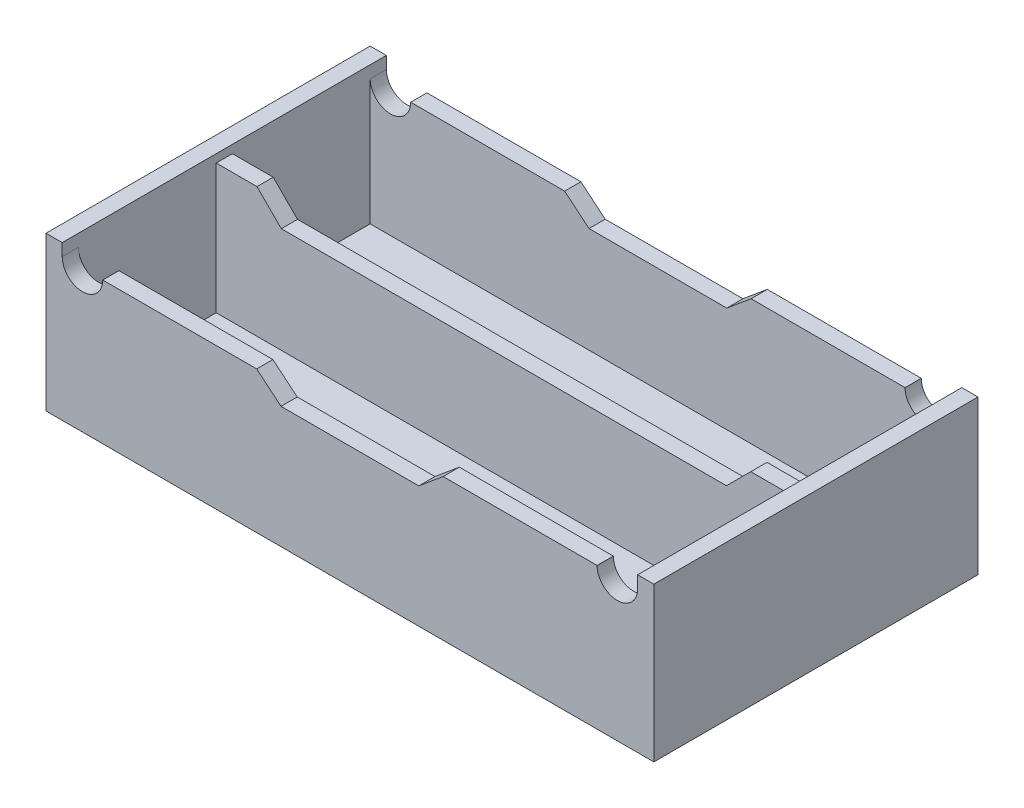
SolidWorks part; units mm, degrees
ref_plane "Front Plane" through (0, 0, 0) normal (0, 0, 1) x (1, 0, 0)
ref_plane "Top Plane" through (0, 0, 0) normal (0, 1, 0) x (1, 0, 0)
ref_plane "Right Plane" through (0, 0, 0) normal (1, 0, 0) x (0, 0, -1)
sketch "Sketch1" plane through (0, 0, 0) normal (0, 1, 0) x (1, 0, 0)
  line L1 (0, 0) -> (75, 0)
  line L2 (0, 0) -> (0, 40)
  line L3 (0, 40) -> (75, 40)
  line L4 (75, 0) -> (75, 40)
  dimension "D1" = 75
  dimension "D2" = 40
extrude "Boss-Extrude1" add sketch "Sketch1" along normal blind 2
sketch "Sketch2" plane through (0, 2, 0) normal (0, 1, 0) x (1, 0, 0)
  line L1 (2, 38) -> (73, 38)
  line L2 (2, 38) -> (2, 21)
  line L3 (2, 21) -> (73, 21)
  line L4 (73, 38) -> (73, 21)
  line L5 (2, 19) -> (73, 19)
  line L6 (2, 19) -> (2, 2)
  line L7 (2, 2) -> (73, 2)
  line L8 (73, 19) -> (73, 2)
  line L9 (0, 40) -> (75, 40)
  line L10 (0, 40) -> (0, 0)
  line L11 (0, 0) -> (75, 0)
  line L12 (75, 40) -> (75, 0)
  point P14 (0, 20)
  dimension "D1" = 2
  dimension "D2" = 2
  dimension "D3" = 2
  dimension "D4" = 2
  dimension "D5" = 2
  dimension "D6" = 1
extrude "Boss-Extrude2" add sketch "Sketch2" along normal blind 17
sketch "Sketch3" plane through (0, 0, 0) normal (0, 0, 1) x (1, 0, 0)
  line L0 (2, 17.5) -> (2, 19)
  line L1 (2, 19) -> (2, 2) construction
  line L2 (2, 19) -> (73, 19)
  line L3 (73, 19) -> (73, 17.5)
  line L4 (73, 19) -> (73, 2) construction
  line L5 (7, 17.5) -> (26, 17.5)
  line L6 (26, 17.5) -> (29, 15)
  line L7 (29, 15) -> (46, 15)
  line L8 (46, 15) -> (49, 17.5)
  line L9 (49, 17.5) -> (68, 17.5)
  arc A0 (2, 17.5) -> (7, 17.5) centre (4.5, 17.5) ccw
  arc A1 (68, 17.5) -> (73, 17.5) centre (70.5, 17.5) ccw
  point P11 (37.5, 15)
  point P21 (37.5, 19)
  dimension "D1" = 5
  dimension "D2" = 17
  dimension "D3" = 3
  dimension "D4" = 1.5
extrude "Cut-Extrude2" cut sketch "Sketch3" against normal blind 17 contours L6 L7 L8 L9 A1 L3 L2 L0 A0 L5
ref_plane "Plane1" through (0, 0, -20) normal (0, 0, 1) x (1, 0, 0)
mirror "Mirror1" about plane through (0, 0, -20) normal (0, 0, 1) of "Cut-Extrude2"
sketch "Sketch4" plane through (0, 0, -19) normal (0, 0, 1) x (1, 0, 0)
  line L0 (2, 18) -> (7.0359, 18)
  line L1 (2, 19) -> (2, 2) construction
  line L2 (7.0359, 18) -> (10.0359, 15)
  line L3 (10.0359, 15) -> (64.9641, 15)
  line L4 (64.9641, 15) -> (67.9641, 18)
  line L5 (67.9641, 18) -> (73, 18)
  line L6 (73, 19) -> (73, 2) construction
  line L7 (46, 15) -> (29, 15) construction
  line L9 (73, 19) -> (2, 19) construction
  line L10 (2, 18) -> (2, 19)
  line L11 (2, 19) -> (73, 19)
  line L12 (73, 19) -> (73, 18)
  dimension "D1" = 1
  dimension "D2" = 3
extrude "Cut-Extrude3" cut sketch "Sketch4" against normal up to next contours L2 L3 L4 L5 L12 L11 L10 L0
sketch "Sketch5" plane through (0, 2, 0) normal (0, 1, 0) x (1, 0, 0)
  line L0 (2, 38) -> (2, 21) construction
  line L1 (2, 19) -> (2, 2) construction
  line L2 (73, 38) -> (2, 38) construction
  circle A0 centre (37.5, 29.5) radius 1.6
  circle A1 centre (37.5, 10.5) radius 1.6
  point P4 (2, 29.5)
  point P5 (2, 10.5)
  point P8 (37.5, 38)
  dimension "D1" = 3.2
extrude "Cut-Extrude4" cut sketch "Sketch5" against normal up to next
ref_plane "Plane2" through (0, 0, -1) normal (0, 0, 1) x (1, 0, 0)
